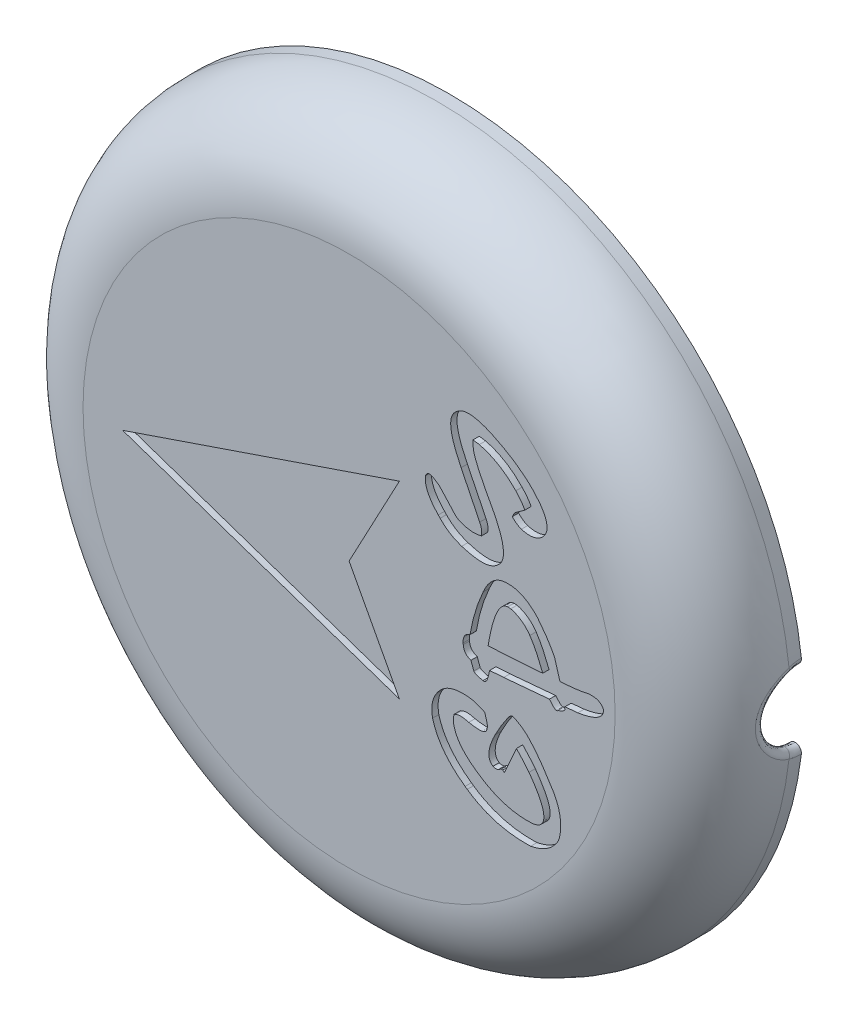
SolidWorks part; units mm, degrees
note: The reader was unsure of these and kept them because the rebuilt part matched: shared geometry of "Croquis5<4>".
material "AISI 1020 Acero laminado en frío"
ref_plane "Alzado" through (0, 0, 0) normal (0, 0, 1) x (1, 0, 0)
ref_plane "Planta" through (0, 0, 0) normal (0, 1, 0) x (1, 0, 0)
ref_plane "Vista lateral" through (0, 0, 0) normal (1, 0, 0) x (0, 0, -1)
sketch "Croquis1" plane through (0, 0, 0) normal (0, 0, 1) x (1, 0, 0)
  line L1 (-19.2, 19.2) -> (19.2, 19.2)
  line L2 (-19.2, 19.2) -> (-19.2, -19.2)
  line L3 (-19.2, -19.2) -> (19.2, -19.2)
  line L4 (19.2, 19.2) -> (19.2, -19.2)
  line L5 (-19.2, 19.2) -> (19.2, -19.2) construction
  line L6 (-19.2, -19.2) -> (19.2, 19.2) construction
  point P0 (0, 0)
  dimension "D1" = 38.4
sketch "Croquis3" plane through (0, 0, 0) normal (0, 0, 1) x (1, 0, 0)
  circle A0 centre (0, 0) radius 27.1529
extrude "Saliente-Extruir1" add sketch "Croquis3" along normal blind 7
fillet "Redondeo1" radius 6 1 edges at (27.1529, 0, 7)
shell "Vaciado1" thickness 1 removed face at (27.1529, 0, 0) outward yes
ref_plane "Plano1" through (0, 0, 1.6) normal (0, 0, 1) x (1, 0, 0)
sketch "Croquis5" plane through (0, 0, 1.6) normal (0, 0, 1) x (1, 0, 0)
  circle A0 centre (16.35, 16.35) radius 3
  circle A1 centre (-16.35, 16.35) radius 3
  circle A3 centre (16.35, -16.35) radius 3
  circle A4 centre (-16.35, -16.35) radius 3
  circle A9 centre (16.35, -16.35) radius 0.6
  circle A10 centre (-16.35, -16.35) radius 0.6
  circle A11 centre (16.35, 16.35) radius 0.6
  circle A12 centre (-16.35, 16.35) radius 0.6
  dimension "D1" = 6
  dimension "D10" = 6
  dimension "D11" = 1.2
  dimension "D2" = 16.35
  dimension "D3" = 16.35
  dimension "D4" = 16.35
  dimension "D5" = 16.35
  dimension "D6" = 16.35
  dimension "D7" = 16.35
  dimension "D8" = 16.35
  dimension "D9" = 16.35
extrude "Saliente-Extruir3" add sketch "Croquis5" along normal up to surface (5.0151 mm away) up to face at (-28.1529, 0, 1)
ref_plane "Plano2" through (28.155, 0, 0) normal (1, 0, 0) x (0, 0, -1)
sketch "Croquis7" plane through (28.155, 0, 0) normal (1, 0, 0) x (0, 0, -1)
  circle A0 centre (0, 0) radius 2.75
  dimension "D1" = 5.5
extrude "Cortar-Extruir1" cut sketch "Croquis7" against normal blind 5
fillet "Redondeo4" radius 0.5 3 edges at (27.9349, -0.3833, 2.7232)
fillet "Redondeo5" radius 0.5 3 edges at (26.8971, -0.3713, 2.7248)
sketch "Croquis8" plane through (0, 0, 8) normal (0, 0, 1) x (1, 0, 0)
  arc A0 (3.6286, -20.8393) -> (0, 21.1529) centre (0, 0) ccw construction
  circle A1 centre (0, 0) radius 21.1529 construction
  arc A2 (3.6286, -18.806) -> (0, 19.1529) centre (0, 0) ccw construction
  arc A3 (4.0076, -20.7698) -> (0, 21.1529) centre (0, 0) ccw construction
  text T0 "GPS" font "@Hand Of Sean" height in points 36
  dimension "D1" = 2
  dimension "D2" = 3.0695
  dimension "D3" = 13.4129
  dimension "D4" = 3.6286
sketch "Croquis9" plane through (0, 0, 8) normal (0, 0, 1) x (1, 0, 0)
  line L0 (-18, 0) -> (4, 0) construction
  line L1 (4, -7.5) -> (-18, -7.5) construction
  line L2 (4, -7.5) -> (4, 7.5) construction
  line L3 (4, 7.5) -> (-18, 7.5) construction
  line L4 (-18, -7.5) -> (-18, 7.5) construction
  line L5 (-18, 0) -> (4, -7.5)
  line L6 (4, -7.5) -> (0, 0)
  line L7 (0, 0) -> (4, 7.5)
  line L8 (4, 7.5) -> (-18, 0)
  point P0 (0, 0)
  dimension "D1" = 4
  dimension "D2" = 22
  dimension "D3" = 15
  dimension "D4" = 0
extrude "Cortar-Extruir2" cut sketch "Croquis9" against normal blind 0.5
extrude "Cortar-Extruir3" cut sketch "Croquis8" against normal blind 0.5
extrude "Cortar-Extruir4" cut sketch "Croquis5<4>" along normal blind 1.5
sketch "Croquis5<4>" plane through (0, 0, 1.6) normal (0, 0, 1) x (1, 0, 0) same geometry as "Croquis5"
sketch "Croquis10" plane through (0, 0, 3.1) normal (0, 0, -1) x (-1, 0, 0)
  circle A0 centre (16.35, 16.35) radius 1.25
  circle A1 centre (-16.35, 16.35) radius 1.25
  circle A2 centre (-16.35, -16.35) radius 1.25
  circle A3 centre (16.35, -16.35) radius 1.25
  circle A4 centre (16.35, 16.35) radius 0.6
  circle A5 centre (16.35, -16.35) radius 0.6
  circle A7 centre (-16.35, -16.35) radius 0.6
  circle A8 centre (-16.35, 16.35) radius 0.6
  dimension "D1" = 2.5
  dimension "D2" = 1.2
extrude "Saliente-Extruir4" add sketch "Croquis10" along normal blind 1.5
